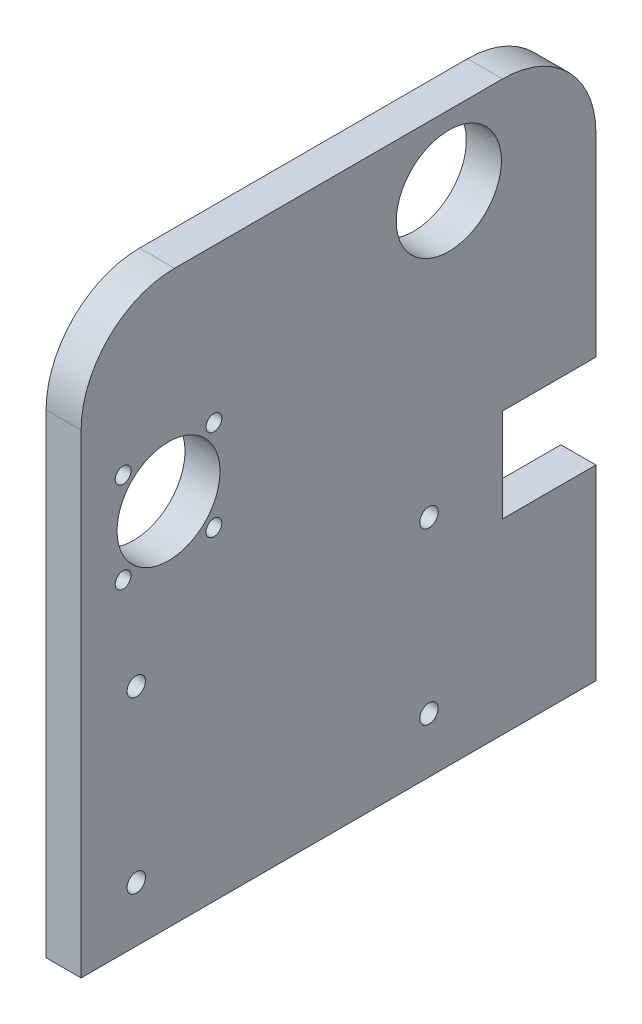
SolidWorks part; units mm, degrees
ref_plane "Front Plane" through (0, 0, 0) normal (0, 0, 1) x (1, 0, 0)
ref_plane "Top Plane" through (0, 0, 0) normal (0, 1, 0) x (1, 0, 0)
ref_plane "Right Plane" through (0, 0, 0) normal (1, 0, 0) x (0, 0, -1)
sketch "Sketch1" plane through (0, 0, 0) normal (0, 1, 0) x (1, 0, 0)
  line L1 (-4.7625, 70) -> (4.7625, 70)
  line L2 (-4.7625, 70) -> (-4.7625, -70)
  line L3 (-4.7625, -70) -> (4.7625, -70)
  line L4 (4.7625, 70) -> (4.7625, -70)
  line L5 (-4.7625, 70) -> (4.7625, -70) construction
  line L6 (-4.7625, -70) -> (4.7625, 70) construction
  point P0 (0, 0)
  dimension "D1" = 140
  dimension "D2" = 9.525
extrude "Boss-Extrude1" add sketch "Sketch1" along normal mid plane 154.4436
fillet "Fillet1" radius 25.4 2 edges at (0, 77.2218, 70) (0, 77.2218, -70)
sketch "Sketch5" plane through (-4.7625, 0, 0) normal (-1, 0, 0) x (0, 0, 1)
  line L1 (-70, 51.8218) -> (-70, -77.2218) construction
  line L2 (-70, -0.9964) -> (-44.6, -0.9964)
  line L3 (-70, -0.9964) -> (-70, -26.3964)
  line L4 (-70, -26.3964) -> (-44.6, -26.3964)
  line L5 (-70, -77.2218) -> (70, -77.2218) construction
  line L6 (-44.6, -0.9964) -> (-44.6, -26.3964)
  dimension "D3" = 25.4
  dimension "D1" = 50.8254
  dimension "D2" = 25.4
sketch "Sketch3" plane through (-4.7625, 0, 0) normal (-1, 0, 0) x (0, 0, 1)
  line L0 (46.229, 23.1718) -> (62.638, 39.5809) construction
  line L2 (-70, 51.8218) -> (-70, -77.2218) construction
  line L3 (-45.4613, 23.1718) -> (44.137, 23.1718) construction
  line L6 (46.229, 46.9613) -> (46.229, -2.4047) construction
  line L7 (-44.6, 77.2218) -> (44.6, 77.2218) construction
  circle A0 centre (-30, 58.1718) radius 14.29
  circle A1 centre (33.8811, 35.5197) radius 2.15
  circle A2 centre (58.5768, 35.5197) radius 2.15
  circle A3 centre (33.8811, 10.824) radius 2.15
  circle A4 centre (58.5768, 10.824) radius 2.15
  circle A5 centre (46.229, 23.1718) radius 14
  circle A6 centre (46.229, 23.1718) radius 17.4625 construction
  dimension "D1" = 28.58
  dimension "D2" = 19.05
  dimension "D3" = 45
  dimension "D4" = 12.3479
  dimension "D7" = 28
  dimension "D8" = 4.3
  dimension "D10" = 35
  dimension "Bolt circle" = 34.925
  dimension "D5" = 83.88
  dimension "D9" = 40
extrude "Cut-Extrude2" cut sketch "Sketch3" against normal blind 28.575
extrude "Cut-Extrude4" cut sketch "Sketch5" against normal through all
ref_axis "Axis1" through (4.7625, 58.1718, -30) along (-1, 0, 0)
hole_wizard "M6 Tapped Hole1" positions "Sketch7" profile "Sketch6" tap size "M6" standard "DIN"
sketch "Sketch7" plane through (0, 0, -44.6) normal (0, 0, -1) x (-1, 0, 0)
  line L1 (-4.7625, -26.3964) -> (4.7625, -26.3964) construction
  point P0 (0, -13.6964)
  dimension "D1" = 12.7
sketch "Sketch6" plane through (0, -13.6964, -44.6) normal (1, 0, 0) x (0, 1, 0)
  line L0 (0, 0) -> (0, 11.5022)
  line L1 (0, 11.5022) -> (2.5, 10)
  line L2 (2.5, 10) -> (2.5, 0)
  line L5 (2.5, 0) -> (0, 0)
  line L10 (0, 11.5022) -> (-2.5, 10) construction
  line L11 (0, -6.35) -> (0, 107.95) construction
  dimension "Tap Drill Dia." = 5
  dimension "Tap Drill Depth" = 10
  dimension "Drill Angle" = 118
cosmetic thread "Hole Thread1" parameters "D1"=10, "D2"=6
hole_wizard "M6 Tapped Hole2" positions "Sketch9" profile "Sketch8" tap size "M6" standard "DIN" end condition through all
sketch "Sketch9" plane through (-4.7625, 0, 0) normal (-1, 0, 0) x (0, 0, 1)
  line L0 (-44.6, -26.3964) -> (-44.6, -0.9964) construction
  line L1 (-70, -26.3964) -> (-70, -77.2218) construction
  line L2 (70, 51.8218) -> (70, -77.2218) construction
  line L3 (-44.6, -0.9964) -> (-70, -0.9964) construction
  line L5 (-70, -77.2218) -> (70, -77.2218) construction
  point P0 (-24.6, -15.9964)
  point P2 (55, -15.9964)
  point P4 (-24.6, -62.2218)
  point P6 (55, -62.2218)
  dimension "D1" = 20
  dimension "D2" = 45.4
  dimension "D3" = 15
  dimension "D4" = 15
  dimension "D5" = 15
  dimension "D6" = 15
  dimension "D7" = 15
  dimension "D8" = 15
sketch "Sketch8" plane through (-4.7625, -15.9964, -24.6) normal (0, 1, 0) x (0, 0, 1)
  line L0 (0, 0) -> (0, 9.525)
  line L1 (0, 9.525) -> (2.5, 9.525)
  line L2 (2.5, 9.525) -> (2.5, 0)
  line L5 (2.5, 0) -> (0, 0)
  line L11 (0, -6.35) -> (0, 107.95) construction
  dimension "Thru Tap Drill Dia." = 5
  dimension "Thru Tap Drill Depth" = 9.525
cosmetic thread "Hole Thread2"
cosmetic thread "Hole Thread3"
cosmetic thread "Hole Thread4"
cosmetic thread "Hole Thread5"
